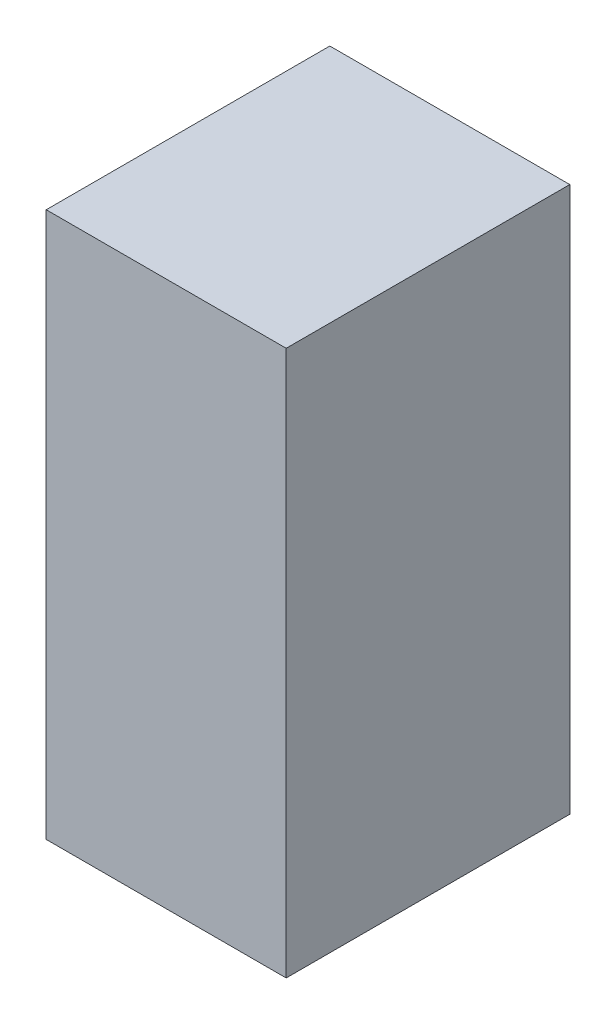
SolidWorks part; units mm, degrees
ref_plane "前视基准面" through (0, 0, 0) normal (0, 0, 1) x (1, 0, 0)
ref_plane "上视基准面" through (0, 0, 0) normal (0, 1, 0) x (1, 0, 0)
ref_plane "右视基准面" through (0, 0, 0) normal (1, 0, 0) x (0, 0, -1)
sketch "草图2" plane through (0, 0, 0) normal (0, 0, 1) x (1, 0, 0)
  line L1 (-11, -25) -> (11, -25)
  line L2 (-11, -25) -> (-11, 25)
  line L3 (-11, 25) -> (11, 25)
  line L4 (11, -25) -> (11, 25)
  line L5 (-11, -25) -> (11, 25) construction
  line L6 (-11, 25) -> (11, -25) construction
  point P0 (0, 0)
  dimension "D1" = 22
  dimension "D2" = 50
extrude "凸台-拉伸1" add sketch "草图2" along normal blind 3
sketch "草图3" plane through (0, 0, 3) normal (0, 0, 1) x (1, 0, 0)
  line L0 (-11, 20.2305) -> (-10.5, 20.2305)
  line L1 (-11, 25) -> (11, 25)
  line L2 (-11, 25) -> (-11, 20.2305)
  line L3 (-11, -25) -> (11, -25)
  line L4 (11, 25) -> (11, -25)
  line L5 (-10.5, 24.5) -> (10.5, 24.5)
  line L6 (-10.5, 24.5) -> (-10.5, 20.2305)
  line L7 (-10.5, -24.5) -> (10.5, -24.5)
  line L8 (10.5, 24.5) -> (10.5, -24.5)
  line L9 (-11, -19.7695) -> (-10.5, -19.7695)
  line L10 (-10.5, -19.7695) -> (-10.5, -24.5)
  line L11 (-11, -19.7695) -> (-11, -25)
  dimension "D1" = 0.5
  dimension "D2" = 0.5
  dimension "D3" = 0.5
  dimension "D4" = 0.5
  dimension "D5" = 40
extrude "凸台-拉伸2" add sketch "草图3" along normal blind 20
sketch "草图4" plane through (0, 0, 3) normal (0, 0, 1) x (1, 0, 0)
  line L0 (0.0791, 0) -> (0.0791, 11.3705) construction
  line L1 (0.0791, 11.3705) -> (0.0791, -13.7359) construction
  line L2 (0.0791, 0) -> (-11.8606, 0) construction
  line L3 (0.0791, 0) -> (11.8606, 0) construction
  line L8 (5.0791, -16.732) -> (5.0791, 16.732)
  line L9 (6.0791, 17.85) -> (6.0791, -17.85)
  line L10 (6.5791, -17.85) -> (6.5791, 17.85)
  line L11 (7.5791, 17.85) -> (7.5791, -17.85)
  line L12 (-3.9209, 21.35) -> (4.0791, 21.35)
  line L13 (-3.9209, 20.35) -> (4.0791, 20.35)
  line L14 (-3.9209, 19.85) -> (4.0791, 19.85)
  line L15 (-2.8029, 18.85) -> (2.961, 18.85)
  line L16 (-7.4209, 17.85) -> (-7.4209, -17.85)
  line L17 (-6.4209, -17.85) -> (-6.4209, 17.85)
  line L18 (-5.9209, 17.85) -> (-5.9209, -17.85)
  line L19 (-4.9209, -16.732) -> (-4.9209, 16.732)
  line L20 (-2.8029, -18.85) -> (2.961, -18.85)
  line L21 (-3.9209, -19.85) -> (4.0791, -19.85)
  line L22 (-3.9209, -20.35) -> (4.0791, -20.35)
  line L23 (-3.9209, -21.35) -> (4.0791, -21.35)
  arc A9 (-3.9209, 20.35) -> (-6.4209, 17.85) centre (-3.9209, 17.85) ccw
  arc A10 (-3.9209, 19.85) -> (-5.9209, 17.85) centre (-3.9209, 17.85) ccw
  arc A12 (-3.9209, 21.35) -> (-7.4209, 17.85) centre (-3.9209, 17.85) ccw
  arc A13 (-3.9209, -21.35) -> (-7.4209, -17.85) centre (-3.9209, -17.85) cw
  arc A14 (-3.9209, -20.35) -> (-6.4209, -17.85) centre (-3.9209, -17.85) cw
  arc A16 (-3.9209, -19.85) -> (-5.9209, -17.85) centre (-3.9209, -17.85) cw
  arc A18 (4.0791, -19.85) -> (6.0791, -17.85) centre (4.0791, -17.85) ccw
  arc A19 (4.0791, -20.35) -> (6.5791, -17.85) centre (4.0791, -17.85) ccw
  arc A20 (4.0791, -21.35) -> (7.5791, -17.85) centre (4.0791, -17.85) ccw
  arc A22 (4.0791, 19.85) -> (6.0791, 17.85) centre (4.0791, 17.85) cw
  arc A23 (4.0791, 20.35) -> (6.5791, 17.85) centre (4.0791, 17.85) cw
  arc A25 (4.0791, 21.35) -> (7.5791, 17.85) centre (4.0791, 17.85) cw
  arc A27 (-2.8029, -18.85) -> (-4.9209, -16.732) centre (-3.9209, -17.85) ccw
  arc A28 (2.961, -18.85) -> (5.0791, -16.732) centre (4.0791, -17.85) cw
  arc A29 (2.961, 18.85) -> (5.0791, 16.732) centre (4.0791, 17.85) ccw
  arc A30 (-2.8029, 18.85) -> (-4.9209, 16.732) centre (-3.9209, 17.85) cw
  circle A31 centre (-3.9209, -17.85) radius 0.5
  circle A32 centre (4.0791, -17.85) radius 0.5
  circle A33 centre (-3.9209, 17.85) radius 0.5
  circle A34 centre (4.0791, 17.85) radius 0.5
extrude "切除-拉伸1" cut sketch "草图4" against normal blind 1 contours A25 L12 A12 L16 A13 L23 A20 L11 L13 A23 L10 A19 L22 A14 L17 A9 region at (7.1265, 0, 3)
extrude "切除-拉伸2" cut sketch "草图4<3>" against normal blind 2 contours A22 L14 A10 L18 A16 L21 A18 L9 L15 L8 L20 L19 region at (5.6643, 0, 3)
sketch "草图4<3>" plane through (0, 0, 3) normal (0, 0, 1) x (1, 0, 0) same geometry as "草图4"
sketch "草图5" plane through (0, 0, 23) normal (0, 0, 1) x (1, 0, 0)
  line L1 (-11, 25) -> (11, 25)
  line L2 (-11, 25) -> (-11, -25)
  line L3 (-11, -25) -> (11, -25)
  line L4 (11, 25) -> (11, -25)
extrude "凸台-拉伸3" add sketch "草图5" along normal blind 3
sketch "草图8" plane through (0, 0, 3) normal (0, 0, 1) x (1, 0, 0)
  circle A0 centre (4.0791, -17.85) radius 0.5 construction
  circle A1 centre (4.0791, 17.85) radius 0.5 construction
  circle A2 centre (-3.9209, 17.85) radius 0.5 construction
  circle A3 centre (-3.9209, -17.85) radius 0.5 construction
  circle A4 centre (4.0791, -17.85) radius 0.5
  circle A5 centre (4.0791, 17.85) radius 0.5
  circle A6 centre (-3.9209, 17.85) radius 0.5
  circle A7 centre (-3.9209, -17.85) radius 0.5
extrude "切除-拉伸3" cut sketch "草图8" against normal blind 1.2
sketch "草图9" plane through (0, -25, 0) normal (0, -1, 0) x (1, 0, 0)
  line L0 (0, 0) -> (0, 25.1925) construction
  line L1 (-11, 13) -> (11.6615, 13) construction
  line L2 (-11, 26) -> (-11, 0) construction
  circle A0 centre (0, 13) radius 0.75
  dimension "D1" = 1.5
extrude "凸台-拉伸4" add sketch "草图9" along normal blind 2
scale "缩放比例1" scale about centroid uniform scaling yes scale factor 10
